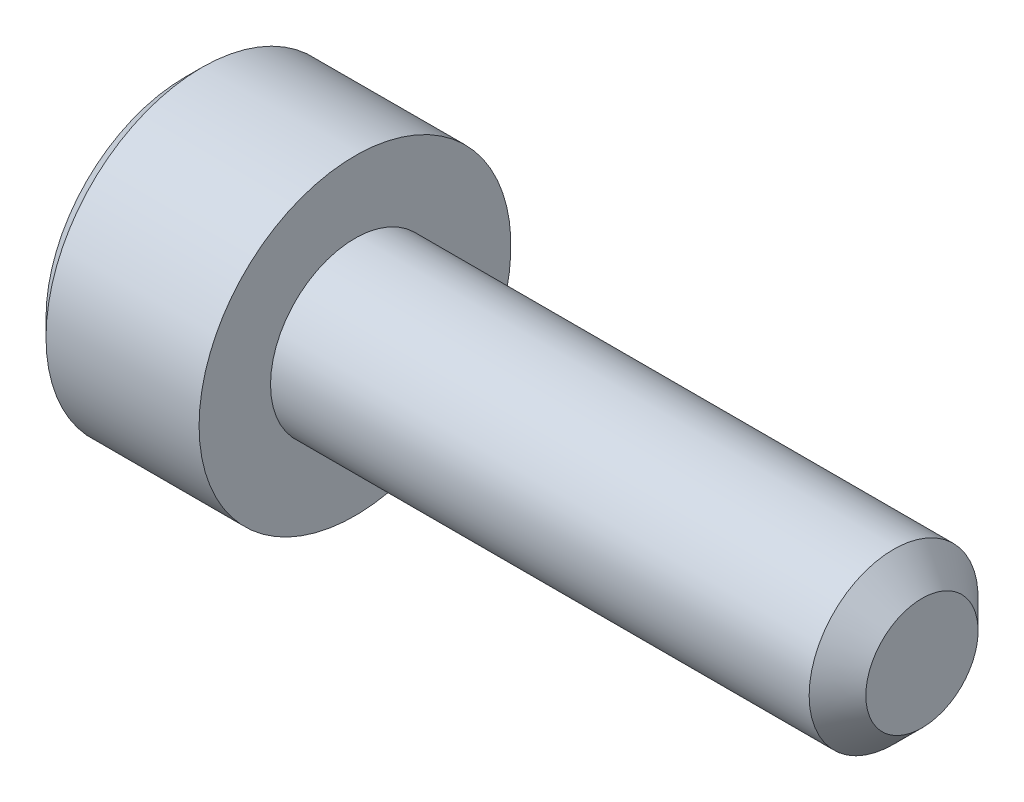
SolidWorks part; units mm, degrees
material "AISI Type 316L stainless steel"
ref_plane "Front Plane" through (0, 0, 0) normal (0, 0, 1) x (1, 0, 0)
ref_plane "Top Plane" through (0, 0, 0) normal (0, 1, 0) x (1, 0, 0)
ref_plane "Right Plane" through (0, 0, 0) normal (1, 0, 0) x (0, 0, -1)
sketch "Sketch1" plane through (0, 0, 0) normal (0, 0, 1) x (1, 0, 0)
  line L0 (-88.7055, 0) -> (96.9812, 0) construction
  line L1 (0, 0) -> (0, 2.75)
  line L2 (0, 2.75) -> (3, 2.75)
  line L4 (13, 0) -> (13, 1.49)
  line L5 (13, 1.49) -> (3, 1.49)
  line L6 (3, 1.49) -> (3, 2.75)
  line L7 (0, 0) -> (13, 0)
  dimension "D1" = 10
  dimension "D2" = 3
  dimension "D3" = 2.75
  dimension "D4" = 1.49
revolve "Revolve1" add sketch "Sketch1" angle 360 about L0
chamfer "Chamfer1" distance 0.5 angle 45 1 edges at (13, 0, 1.49)
chamfer "Chamfer2" distance 0.3 angle 45 1 edges at (0, 0, 2.75)
sketch "Sketch3" plane through (0, 0, 0) normal (1, 0, 0) x (0, 0, -1)
  line L1 (-1.4434, 0) -> (-0.7217, -1.25)
  line L2 (-0.7217, -1.25) -> (0.7217, -1.25)
  line L3 (0.7217, -1.25) -> (1.4434, 0)
  line L4 (1.4434, 0) -> (0.7217, 1.25)
  line L5 (0.7217, 1.25) -> (-0.7217, 1.25)
  line L6 (-0.7217, 1.25) -> (-1.4434, 0)
  circle A0 centre (0, 0) radius 1.25 construction
extrude "Cut-Extrude1" cut sketch "Sketch3" along normal blind 2.5
chamfer "Chamfer3" distance 0.3 angle 45 6 edges at (0, 1.25, 0) (0, 0.625, 1.0825) (0, -0.625, 1.0825) (0, -1.25, 0) (0, -0.625, -1.0825) (0, 0.625, -1.0825)
sketch "Sketch5" plane through (13, 0, 0) normal (1, 0, 0) x (0, 0, -1)
  circle A0 centre (0, 0) radius 1.49
curve "Helix/Spiral1" pitch 0.5 height 20 turns 40
sketch "Sketch8" plane through (0, 0, 0) normal (0, 1, 0) x (1, 0, 0)
  line L0 (13, 1.49) -> (13, 1.1111) construction
  line L1 (13.0625, 1.2194) -> (13.3281, 1.6794)
  line L2 (13.3281, 1.6794) -> (12.6719, 1.6794)
  line L3 (12.6719, 1.6794) -> (12.9375, 1.2194)
  line L4 (13, -0.99) -> (13, 0.99) construction
  circle A0 centre (13, 1.49) radius 0.1894 construction
  arc A1 (13.0625, 1.2194) -> (12.9375, 1.2194) centre (13, 1.2555) cw
  dimension "D2" = 0.0722
  dimension "D1" = 0.3789
sweep "Cut-Sweep1" [suppressed] cut profiles "Sketch8" path "Helix/Spiral1"
equation "\"length\"= 10"
equation "\"D1@Sketch1\"=\"length\""
